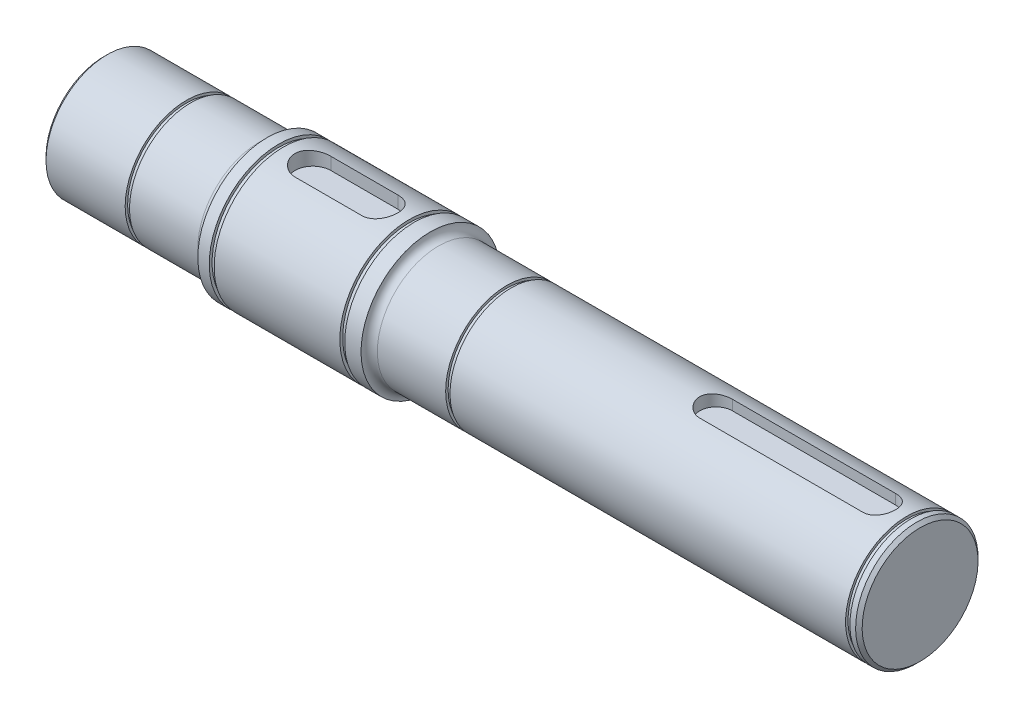
SolidWorks part; units mm, degrees
ref_plane "Front" through (0, 0, 0) normal (0, 0, 1) x (1, 0, 0)
ref_plane "Top" through (0, 0, 0) normal (0, 1, 0) x (1, 0, 0)
ref_plane "Right" through (0, 0, 0) normal (1, 0, 0) x (0, 0, -1)
sketch "Esquisse1" plane through (0, 0, 0) normal (0, 0, 1) x (1, 0, 0)
  line L0 (0, 0) -> (0, 37.5)
  line L1 (0, 37.5) -> (95, 37.5)
  line L3 (100, 42.5) -> (200, 42.5)
  line L5 (205, 37.5) -> (500, 37.5)
  line L6 (500, 37.5) -> (500, 0)
  line L7 (500, 0) -> (0, 0)
  arc A0 (100, 42.5) -> (95, 37.5) centre (95, 42.5) cw
  arc A1 (200, 42.5) -> (205, 37.5) centre (205, 42.5) ccw
  dimension "D4" = 5
  dimension "D6" = 5
  dimension "D1" = 37.5
  dimension "D2" = 100
  dimension "D3" = 500
  dimension "D5" = 42.5
  dimension "D7" = 100
revolve "Révolution1" add sketch "Esquisse1" angle 360 about L7
ref_plane "Plan1" through (110, 0, 0) normal (1, 0, 0) x (0, 0, -1)
ref_plane "Plan2" through (190, 0, 0) normal (1, 0, 0) x (0, 0, -1)
sketch "Esquisse2" plane through (110, 0, 0) normal (1, 0, 0) x (0, 0, -1)
  circle A0 centre (0, 0) radius 42.5 construction
  circle A2 centre (0, 0) radius 42.5
  circle A3 centre (0, 0) radius 40.75
  dimension "D1" = 1.75
extrude "Enlèv. mat.-Extru.1" cut sketch "Esquisse2" against normal blind 3
sketch "Esquisse3" plane through (190, 0, 0) normal (1, 0, 0) x (0, 0, -1)
  circle A0 centre (0, 0) radius 42.5 construction
  circle A1 centre (0, 0) radius 42.5
  circle A2 centre (0, 0) radius 40.75
  dimension "D1" = 1.75
extrude "Enlèv. mat.-Extru.2" cut sketch "Esquisse3" against normal blind 3
ref_plane "Plan3" through (0, 42.5, 0) normal (0, 1, 0) x (1, 0, 0)
sketch "Esquisse4" plane through (0, 42.5, 0) normal (0, 1, 0) x (1, 0, 0)
  line L0 (148.5, 42.5) -> (148.5, 0) construction
  line L1 (187, 42.5) -> (110, 42.5) construction
  line L2 (128, 0) -> (169, 0) construction
  line L3 (128, 11) -> (169, 11)
  line L4 (128, -11) -> (169, -11)
  arc A0 (128, 11) -> (128, -11) centre (128, 0) ccw
  arc A1 (169, -11) -> (169, 11) centre (169, 0) ccw
  point P6 (148.5, 0)
  dimension "D2" = 11
  dimension "D1" = 41
extrude "Enlèv. mat.-Extru.3" cut sketch "Esquisse4" against normal blind 9
ref_plane "Plan4" through (0, 37.5, 0) normal (0, 1, 0) x (1, 0, 0)
sketch "Esquisse5" plane through (0, 37.5, 0) normal (0, 1, 0) x (1, 0, 0)
  line L0 (500, 0) -> (425, 0) construction
  line L1 (500, -37.5) -> (500, 37.5) construction
  line L2 (475, 0) -> (375, 0) construction
  line L3 (475, -10) -> (375, -10)
  line L4 (475, 10) -> (375, 10)
  arc A0 (475, -10) -> (475, 10) centre (475, 0) ccw
  arc A1 (375, 10) -> (375, -10) centre (375, 0) ccw
  point P7 (425, 0)
  dimension "D2" = 10
  dimension "D1" = 75
  dimension "D3" = 100
extrude "Enlèv. mat.-Extru.4" cut sketch "Esquisse5" against normal blind 7.5
chamfer "Chanfrein1" distance 2 angle 45 2 edges at (500, 37.5, 0) (0, 37.5, 0)
ref_plane "Plan5" through (494.5, 0, 0) normal (1, 0, 0) x (0, 0, -1)
sketch "Esquisse6" plane through (494.5, 0, 0) normal (1, 0, 0) x (0, 0, -1)
  circle A0 centre (0, 0) radius 37.5 construction
  circle A1 centre (0, 0) radius 37.5
  circle A2 centre (0, 0) radius 36
  dimension "D1" = 1.5
extrude "Enlèv. mat.-Extru.5" cut sketch "Esquisse6" against normal blind 2.65
ref_plane "Plan6" through (50.5, 0, 0) normal (-1, 0, 0) x (0, 0, 1)
sketch "Esquisse7" plane through (50.5, 0, 0) normal (-1, 0, 0) x (0, 0, 1)
  circle A0 centre (0, 0) radius 37.5 construction
  circle A1 centre (0, 0) radius 37.5
  circle A2 centre (0, 0) radius 36
  dimension "D1" = 1.5
extrude "Enlèv. mat.-Extru.6" cut sketch "Esquisse7" against normal blind 2.65
ref_plane "Plan8" through (249.5, 0, 0) normal (-1, 0, 0) x (0, 0, 1)
sketch "Esquisse8" plane through (249.5, 0, 0) normal (-1, 0, 0) x (0, 0, 1)
  circle A0 centre (0, 0) radius 37.5 construction
  circle A1 centre (0, 0) radius 37.5
  circle A2 centre (0, 0) radius 36
  dimension "D1" = 1.5
extrude "Enlèv. mat.-Extru.7" cut sketch "Esquisse8" along normal blind 2.65
